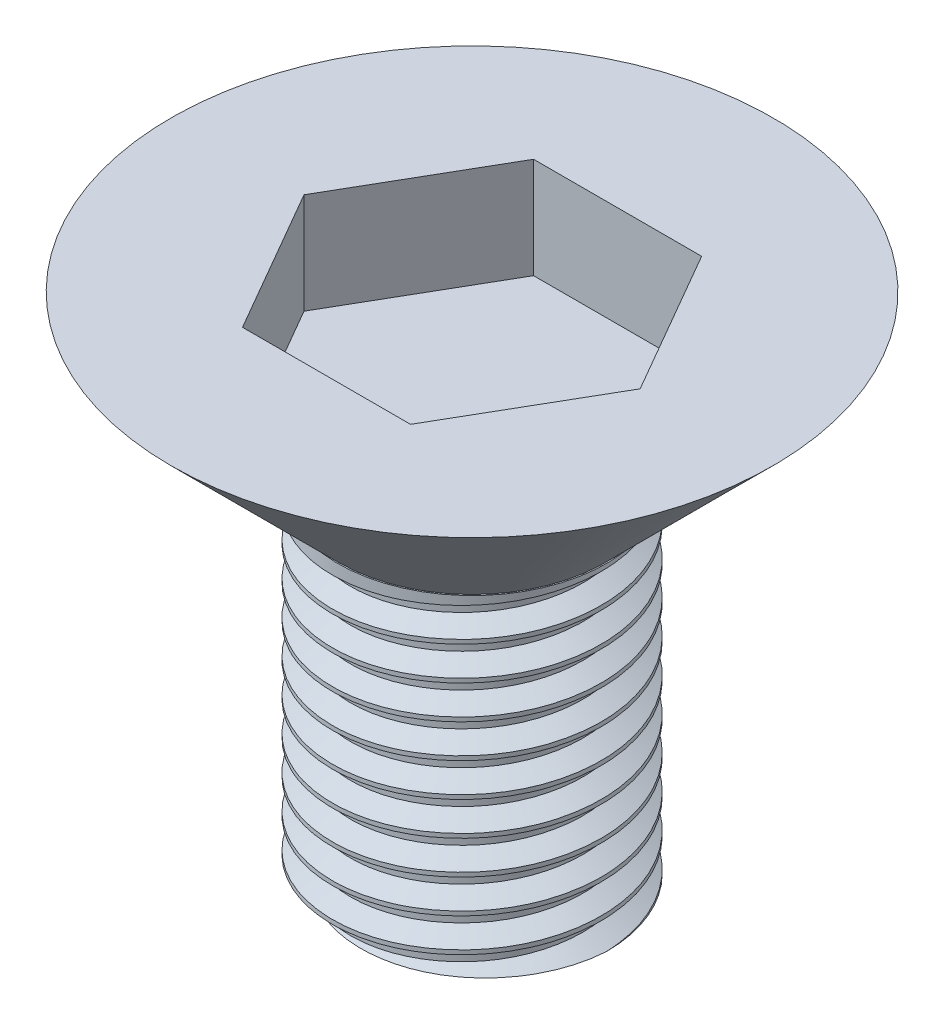
SolidWorks part; units mm, degrees
ref_plane "Alzado" through (0, 0, 0) normal (0, 0, 1) x (1, 0, 0)
ref_plane "Planta" through (0, 0, 0) normal (0, 1, 0) x (1, 0, 0)
ref_plane "Vista lateral" through (0, 0, 0) normal (1, 0, 0) x (0, 0, -1)
sketch "Croquis24" plane through (0, 0, 0) normal (0, 1, 0) x (1, 0, 0)
  circle A0 centre (0, 0) radius 8.96
  dimension "D1" = 17.92
extrude "Saliente-Extruir1" add sketch "Croquis24" against normal blind 5 draft 45
sketch "Croquis26" plane through (0, -5, 0) normal (0, -1, 0) x (1, 0, 0)
  circle A0 centre (0, 0) radius 4
  dimension "D1" = 8
extrude "Saliente-Extruir2" add sketch "Croquis26" along normal blind 10
thread "Rosca1" pitch 1 start angle 0, offset 1, length 0, pitch 1, diameter 8
ref_plane "Plano1" through (4, -16, 0) normal (0, 0, 1) x (1, 0, 0)
sketch "Perfil de rosca1" plane through (4, -16, 0) normal (0, 0, 1) x (1, 0, 0)
  line L0 (0, 0) -> (0, 1) construction
  line L11 (0, 0) -> (0, 0.875)
  line L12 (0, 0.875) -> (-0.5413, 0.5625)
  line L13 (-0.5413, 0.5625) -> (-0.5413, 0.3125)
  line L15 (-0.5413, 0.3125) -> (0, 0)
  line L17 (-0.5413, 0.4375) -> (0, 0.4375) construction
  point P2 (0, 0)
  dimension "Pitch" = 1
  dimension "Profile_Angle" = 60
  dimension "Profile_Land" = 0.25
  dimension "Profile_Height" = 0.5413
sketch "Croquis33" plane through (0, 0, 0) normal (0, 1, 0) x (1, 0, 0)
  line L1 (5, 0) -> (2.5, 4.3301)
  line L2 (2.5, 4.3301) -> (-2.5, 4.3301)
  line L3 (-2.5, 4.3301) -> (-5, 0)
  line L4 (-5, 0) -> (-2.5, -4.3301)
  line L5 (-2.5, -4.3301) -> (2.5, -4.3301)
  line L6 (2.5, -4.3301) -> (5, 0)
  circle A0 centre (0, 0) radius 4.3301 construction
  dimension "D1" = 5
extrude "Cortar-Extruir2" cut sketch "Croquis33" against normal blind 3
